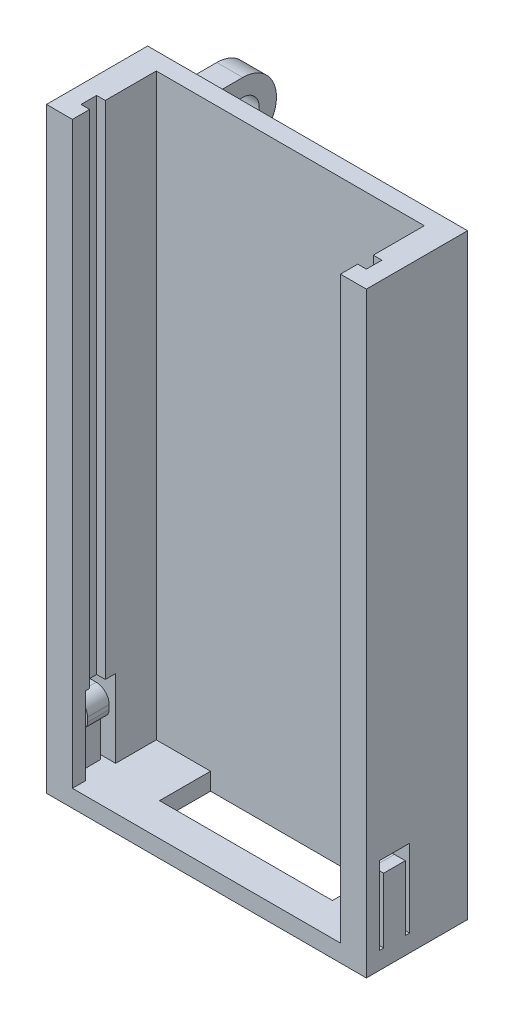
SolidWorks part; units mm, degrees
ref_plane "Front Plane" through (0, 0, 0) normal (0, 0, 1) x (1, 0, 0)
ref_plane "Top Plane" through (0, 0, 0) normal (0, 1, 0) x (1, 0, 0)
ref_plane "Right Plane" through (0, 0, 0) normal (1, 0, 0) x (0, 0, -1)
sketch "Sketch1" plane through (0, 0, 0) normal (0, 1, 0) x (1, 0, 0)
  line L1 (0, 0) -> (37, 0)
  line L2 (0, 0) -> (0, 11.7)
  line L3 (0, 11.7) -> (37, 11.7)
  line L4 (37, 0) -> (37, 11.7)
  dimension "D1" = 37
  dimension "D2" = 11.7
extrude "Boss-Extrude1" add sketch "Sketch1" along normal blind 69
sketch "Sketch2" plane through (0, 69, 0) normal (0, 1, 0) x (1, 0, 0)
  line L0 (3, 0) -> (3, 2)
  line L1 (0, 0) -> (37, 0) construction
  line L2 (3, 2) -> (2, 2)
  line L4 (3, 9.7) -> (34, 9.7)
  line L7 (35, 2) -> (34, 2)
  line L8 (34, 2) -> (34, 0)
  line L9 (3, 0) -> (34, 0)
  line L10 (37, 11.7) -> (0, 11.7) construction
  line L13 (3, 9.7) -> (3, 3.8)
  line L14 (3, 3.8) -> (2, 3.8)
  line L15 (2, 3.8) -> (2, 2)
  line L16 (35, 2) -> (35, 3.8)
  line L17 (35, 3.8) -> (34, 3.8)
  line L18 (34, 3.8) -> (34, 9.7)
  point P11 (18.5, 0)
  point P12 (18.5, 0)
  dimension "D1" = 2
  dimension "D2" = 1.8
  dimension "D3" = 2
  dimension "D4" = 33
  dimension "D5" = 1
extrude "Cut-Extrude1" cut sketch "Sketch2" against normal blind 67
sketch "Sketch3" plane through (0, 2, 0) normal (0, 1, 0) x (1, 0, 0)
  line L0 (34, 9.7) -> (3, 9.7) construction
  line L1 (9.275, 9.7) -> (29.275, 9.7)
  line L2 (9.275, 9.7) -> (9.275, 3.8)
  line L3 (9.275, 3.8) -> (29.275, 3.8)
  line L4 (29.275, 9.7) -> (29.275, 3.8)
  line L5 (35, 3.8) -> (34, 3.8) construction
  line L6 (3, 9.7) -> (3, 3.8) construction
  dimension "D1" = 20
  dimension "D2" = 6.275
extrude "Cut-Extrude2" cut sketch "Sketch3" against normal blind 67
sketch "Sketch4" plane through (37, 0, 0) normal (1, 0, 0) x (0, 0, -1)
  line L0 (11.7, 69) -> (11.7, 0) construction
  line L1 (0, 69) -> (11.7, 69) construction
  line L2 (11.7, 63.35) -> (19.7, 63.35)
  line L3 (19.7, 55.55) -> (11.7, 55.55)
  line L4 (11.7, 27.35) -> (19.7, 27.35)
  line L5 (19.7, 19.55) -> (11.7, 19.55)
  line L6 (11.7, 63.35) -> (11.7, 55.55)
  line L7 (11.7, 27.35) -> (11.7, 19.55)
  circle A0 centre (19.7, 59.45) radius 1.9
  circle A1 centre (19.7, 23.45) radius 1.9
  arc A2 (19.7, 63.35) -> (19.7, 55.55) centre (19.7, 59.45) cw
  arc A3 (19.7, 27.35) -> (19.7, 19.55) centre (19.7, 23.45) cw
  dimension "D4" = 3.8
  dimension "D5" = 2
  dimension "D6" = 2
  dimension "D1" = 8
  dimension "D2" = 36
  dimension "D3" = 9.55
extrude "Boss-Extrude2" add sketch "Sketch4" against normal blind 3 from offset 34 offset against normal yes
fillet "Fillet1" radius 2 6 edges at (1.5, 19.55, -11.7) (1.5, 27.35, -11.7) (1.5, 55.55, -11.7) (1.5, 63.35, -11.7) (3, 23.45, -11.7) (3, 59.45, -11.7)
sketch "Sketch5" plane through (37, 0, 0) normal (1, 0, 0) x (0, 0, -1)
  line L0 (0, 69) -> (0, 0) construction
  line L1 (1.5, 2) -> (5, 2)
  line L2 (1.5, 2) -> (1.5, 11)
  line L3 (1.5, 11) -> (5, 11)
  line L4 (5, 2) -> (5, 11)
  line L5 (0, 0) -> (11.7, 0) construction
  dimension "D1" = 1.5
  dimension "D2" = 2
  dimension "D3" = 3.5
  dimension "D4" = 9
extrude "Cut-Extrude3" cut sketch "Sketch5" against normal blind 40
sketch "Sketch6" plane through (0, 0, -5) normal (0, 0, 1) x (1, 0, 0)
  line L0 (37, 2) -> (37, 9.5)
  line L1 (37, 69) -> (37, 0) construction
  line L2 (37, 9.5) -> (35.75, 9.5)
  line L3 (34.25, 8) -> (34.25, 7.5)
  line L4 (35.25, 6.5) -> (35.25, 2)
  line L5 (35.25, 2) -> (37, 2)
  arc A0 (35.75, 9.5) -> (34.25, 8) centre (35.75, 8) ccw
  arc A1 (34.25, 7.5) -> (35.25, 6.5) centre (35.25, 7.5) ccw
  dimension "D5" = 1
  dimension "D1" = 7.5
  dimension "D2" = 4.5
  dimension "D3" = 1.25
  dimension "D4" = 1.75
extrude "Boss-Extrude3" add sketch "Sketch6" along normal blind 2.5 from offset 0.5
ref_plane "Plane1" through (18.5, 0, 0) normal (1, 0, 0) x (0, 0, -1)
mirror "Mirror1" about plane through (18.5, 0, 0) normal (1, 0, 0) of "Boss-Extrude3"
